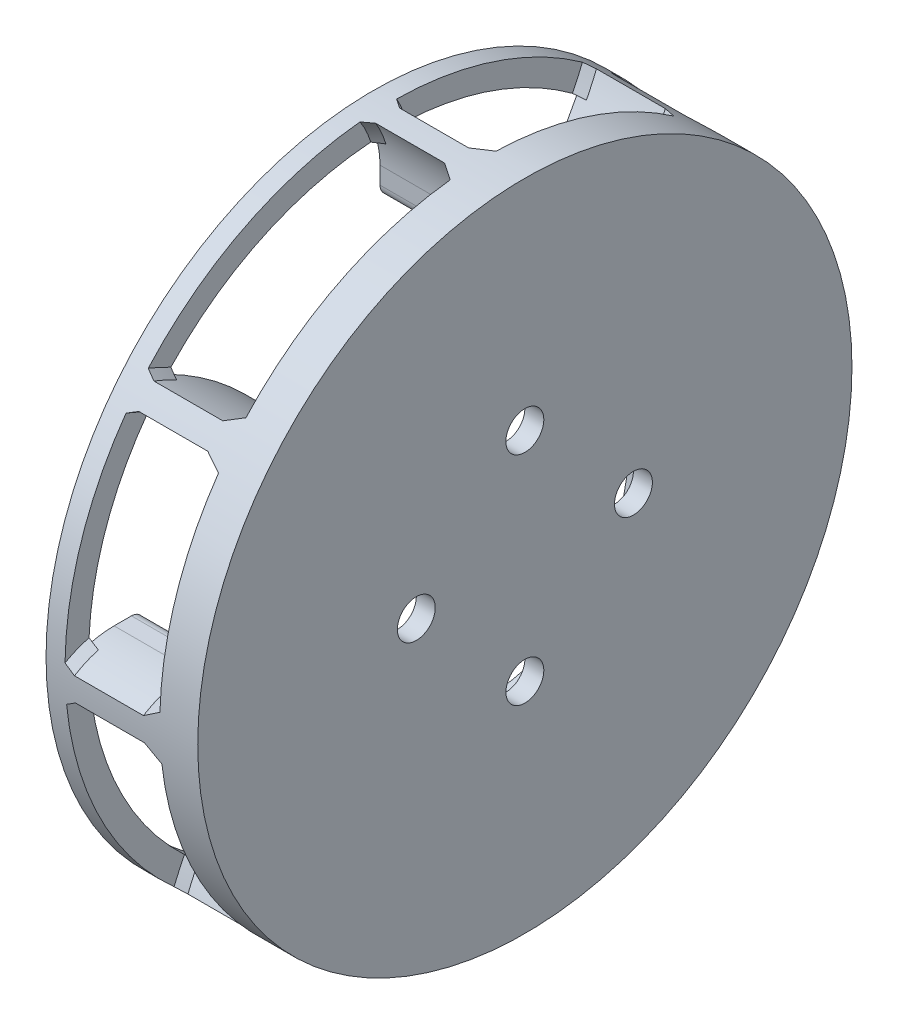
SolidWorks part; units mm, degrees
ref_plane "Front Plane" through (0, 0, 0) normal (0, 0, 1) x (1, 0, 0)
ref_plane "Top Plane" through (0, 0, 0) normal (0, 1, 0) x (1, 0, 0)
ref_plane "Right Plane" through (0, 0, 0) normal (1, 0, 0) x (0, 0, -1)
sketch "Sketch1" plane through (0, 0, 0) normal (1, 0, 0) x (0, 0, -1)
  circle A0 centre (0, 0) radius 34.5
  circle A1 centre (0, 11.45) radius 2
  circle A2 centre (11.45, 0) radius 2
  circle A3 centre (0, -11.45) radius 2
  circle A4 centre (-11.45, 0) radius 2
  dimension "D2" = 69
  dimension "D3" = 4
  dimension "D4" = 18.9
  dimension "D1" = 4
extrude "Boss-Extrude1" add sketch "Sketch1" along normal blind 4
sketch "Sketch2" plane through (0, 0, 0) normal (-1, 0, 0) x (0, 0, 1)
  circle A0 centre (0, 0) radius 14.9
  dimension "D1" = 29.8
extrude "Cut-Extrude1" cut sketch "Sketch2" against normal blind 2
sketch "Sketch3" plane through (0, 0, 0) normal (-1, 0, 0) x (0, 0, 1)
  line L0 (15.5302, 15.5302) -> (12.9641, 12.9641)
  line L1 (15.5302, 15.5302) -> (37.9808, -6.9205) construction
  line L2 (0, -1000) -> (0, 49000) construction
  line L3 (14.7601, 11.168) -> (17.3262, 13.7341)
  line L4 (-1.27, 29.3226) -> (-1.27, 27.496)
  line L5 (1.27, 27.496) -> (1.27, 29.3226)
  arc A0 (15.5302, 15.5302) -> (26.125, 22.5329) centre (37.9808, -6.9205) cw
  circle A1 centre (0, 0) radius 34.5 construction
  circle A2 centre (0, 0) radius 14.9 construction
  arc A3 (12.9641, 12.9641) -> (14.7601, 11.168) centre (13.8621, 12.0661) ccw
  arc A4 (27.712, 20.5498) -> (17.3262, 13.7341) centre (39.6023, -8.8898) ccw
  arc A5 (26.125, 22.5329) -> (27.712, 20.5498) centre (0, 0) cw
  arc A6 (-1.27, 27.496) -> (1.27, 27.496) centre (0, 27.496) ccw
  arc A7 (0.2014, 34.4994) -> (-1.27, 29.3226) centre (8.5725, 29.3226) ccw
  arc A8 (2.7414, 34.3909) -> (1.27, 29.3226) centre (11.1119, 29.2131) ccw
  arc A9 (0.2014, 34.4994) -> (2.7414, 34.3909) centre (0, 0) cw
  dimension "D1" = 31.75
  dimension "D5" = 1.27
  dimension "D7" = 26.226
  dimension "D8" = 1.27
  dimension "D9" = 9.8425
  dimension "D2" = 3.434
  dimension "D3" = 2.54
  dimension "D4" = 45
  dimension "D6" = 2.54
  dimension "D11" = 2.54
extrude "Boss-Extrude2" add sketch "Sketch3" along normal blind 10
ref_axis "Axis1" through (4, 0, 0) along (-1, 0, 0)
pattern_circular "CirPattern4" count 4 over 360 about axis through (4, 0, 0) along (-1, 0, 0) of "Boss-Extrude2"
chamfer "Chamfer3" distance 1 angle 60 40 edges at (0, -16.0432, 12.4511) (0, -12.9641, 11.168) (0, -14.2471, 14.2471) (0, -20.4739, 19.5667) (0, -12.4511, -16.0432) (0, -11.168, -12.9641) (0, -14.2471, -14.2471) (0, -19.5667, -20.4739) (0, 22.1825, -17.6548) (0, -22.1825, 17.6548) (0, -17.6548, -22.1825) (0, 16.0432, -12.4511) (0, 12.9641, -11.168) (0, 14.2471, -14.2471) (0, 20.4739, -19.5667) (0, 12.4511, 16.0432) (0, 11.168, 12.9641) (0, 14.2471, 14.2471) (0, 28.4093, 1.27) (0, 26.226, 0) (0, 28.4093, -1.27) (0, 32.0135, -0.895) (0, 31.9572, 1.6597) (0, 1.6597, -31.9572) (0, -1.27, 28.4093) (0, 0, 26.226) (0, 1.27, 28.4093) (0, 0.895, 32.0135) (0, -28.4093, -1.27) (0, -26.226, 0) (0, -28.4093, 1.27) (0, -32.0135, 0.895) (0, -31.9572, -1.6597) (0, 1.27, -28.4093) (0, 0, -26.226) (0, -1.27, -28.4093) (0, -0.895, -32.0135) (0, -1.6597, 31.9572) first distance on face at (0, 0, 14.9)
sketch "Sketch4" plane through (-10, 0, 0) normal (-1, 0, 0) x (0, 0, 1)
  circle A0 centre (0, 0) radius 34.5
  circle A1 centre (0, 0) radius 32
  circle A3 centre (0, 0) radius 34.5 construction
  dimension "D1" = 2.5
extrude "Boss-Extrude3" add sketch "Sketch4" along normal blind 2
chamfer "Chamfer4" distance 1 angle 30 16 edges at (-10, -2.1178, 33.2107) (-10, -24.9216, 22.0195) (-10, -33.282, 0.4385) (-10, 22.0195, 24.9216) (-10, 0.4385, 33.282) (-10, 20.0458, 26.5335) (-10, 33.2107, 2.1178) (-10, 26.5335, -20.0458) (-10, 2.1178, -33.2107) (-10, -20.0458, -26.5335) (-10, -33.2107, -2.1178) (-10, -26.5335, 20.0458) (-10, -22.0195, -24.9216) (-10, -0.4385, -33.282) (-10, 24.9216, -22.0195) (-10, 33.282, -0.4385) first distance on face at (-6.6928, -1.8328, 31.9069) first distance on face at (-6.6928, -21.2896, 19.6944) first distance on face at (-6.6928, -31.957, 0.716) first distance on face at (-7.5196, 19.6944, 21.2896) first distance on face at (-6.6928, 0.716, 31.957) first distance on face at (-7.5196, 17.7829, 22.9759) first distance on face at (-6.6928, 31.9069, 1.8328) first distance on face at (-6.6928, 22.9759, -17.7829) first distance on face at (-6.6928, 1.8328, -31.9069) first distance on face at (-6.6928, -17.7829, -22.9759) first distance on face at (-6.6928, -31.9069, -1.8328) first distance on face at (-6.6928, -22.9759, 17.7829) first distance on face at (-6.6928, -19.6944, -21.2896) first distance on face at (-6.6928, -0.716, -31.957) first distance on face at (-6.6928, 21.2896, -19.6944) first distance on face at (-6.6928, 31.957, -0.716)
